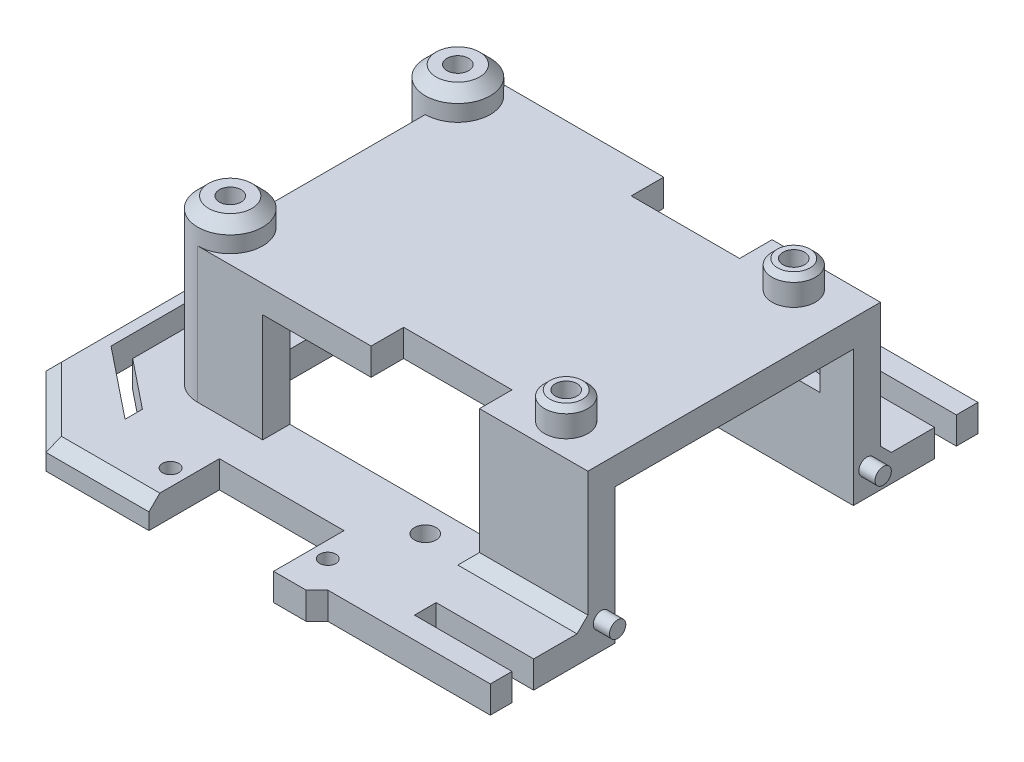
SolidWorks part; units mm, degrees
material "Plain Carbon Steel"
ref_plane "Front Plane" through (0, 0, 0) normal (0, 0, 1) x (1, 0, 0)
ref_plane "Top Plane" through (0, 0, 0) normal (0, 1, 0) x (1, 0, 0)
ref_plane "Right Plane" through (0, 0, 0) normal (1, 0, 0) x (0, 0, -1)
sketch "Sketch1" plane through (0, 0, 0) normal (0, 1, 0) x (1, 0, 0)
  line L0 (0, 0) -> (148.3177, 0) construction
  line L1 (0, 34) -> (0, -34)
  line L2 (0, -34) -> (13, -47)
  line L3 (13, -47) -> (32, -47)
  line L4 (32, -47) -> (32, -34)
  line L5 (32, -34) -> (55, -34)
  line L6 (55, -34) -> (55, -47)
  line L7 (55, -47) -> (61, -47)
  line L8 (61, -47) -> (63, -45)
  line L9 (63, -45) -> (93, -45)
  line L10 (93, -45) -> (93, -41)
  line L11 (93, -41) -> (75, -41)
  line L12 (75, -41) -> (75, -37)
  line L13 (75, -37) -> (93, -37)
  line L14 (93, -37) -> (93, -22)
  line L15 (93, -22) -> (33, -22)
  line L16 (33, -22) -> (21, -10)
  line L17 (21, -10) -> (21, 10)
  line L18 (33, 22) -> (21, 10)
  line L19 (93, 22) -> (33, 22)
  line L20 (93, 37) -> (93, 22)
  line L21 (75, 37) -> (93, 37)
  line L22 (75, 41) -> (75, 37)
  line L23 (93, 41) -> (75, 41)
  line L24 (93, 45) -> (93, 41)
  line L25 (63, 45) -> (93, 45)
  line L26 (61, 47) -> (63, 45)
  line L27 (55, 47) -> (61, 47)
  line L28 (55, 34) -> (55, 47)
  line L29 (32, 34) -> (55, 34)
  line L30 (32, 47) -> (32, 34)
  line L31 (13, 47) -> (32, 47)
  line L32 (0, 34) -> (13, 47)
  circle A0 centre (13, -10) radius 2
  circle A1 centre (29, -40) radius 1.5
  circle A2 centre (58, -40) radius 1.5
  circle A3 centre (63, -27) radius 2
  circle A4 centre (13, 10) radius 2
  circle A5 centre (29, 40) radius 1.5
  circle A6 centre (58, 40) radius 1.5
  circle A7 centre (63, 27) radius 2
  point P22 (21, 0)
  point P44 (0, 0)
  dimension "D17" = 4
  dimension "D18" = 3
  dimension "D19" = 4
  dimension "D20" = 3
  dimension "D1" = 34
  dimension "D2" = 13
  dimension "D3" = 22
  dimension "D4" = 37
  dimension "D5" = 23
  dimension "D6" = 2
  dimension "D7" = 6
  dimension "D8" = 2
  dimension "D9" = 43
  dimension "D10" = 4
  dimension "D11" = 93
  dimension "D12" = 10
  dimension "D13" = 45
  dimension "D14" = 72
  dimension "D15" = 43
  dimension "D16" = 61
  dimension "D21" = 3
  dimension "D22" = 10
  dimension "D23" = 3
  dimension "D24" = 30
  dimension "D25" = 54
  dimension "D26" = 6
  dimension "D27" = 6
  dimension "D28" = 80
extrude "Boss-Extrude1" add sketch "Sketch1" along normal blind 5
sketch "Sketch2" plane through (0, 5, 0) normal (0, 1, 0) x (1, 0, 0)
  line L0 (0, 0) -> (79.458, 0) construction
  line L1 (4, 26) -> (4, 12)
  line L2 (8, -8) -> (4, -8)
  line L3 (8, -8) -> (8, 8)
  line L4 (8, 8) -> (4, 8)
  line L5 (4, -8) -> (4, 8)
  line L6 (8, -8) -> (4, 8) construction
  line L7 (8, 8) -> (4, -8) construction
  line L8 (4, 12) -> (8, 12)
  line L9 (8, 12) -> (8, 26)
  line L10 (8, 26) -> (17, 33.2058)
  line L11 (17, 33.2058) -> (17, 36.4083)
  line L12 (17, 36.4083) -> (4, 26)
  line L14 (32, 34) -> (32, 47) construction
  line L16 (0, 34) -> (0, -34) construction
  line L18 (8, -8) -> (4, 8) construction
  line L19 (8, 8) -> (4, -8) construction
  line L20 (17, -36.4083) -> (4, -26)
  line L21 (4, -12) -> (8, -12)
  line L22 (8, -8) -> (4, -8)
  line L23 (8, 8) -> (4, 8)
  line L24 (8, -26) -> (17, -33.2058)
  line L25 (8, -12) -> (8, -26)
  line L26 (4, -26) -> (4, -12)
  line L27 (17, -33.2058) -> (17, -36.4083)
  circle A0 centre (13, 10) radius 2 construction
  point P3 (6, 0)
  point P16 (0, 0)
  point P19 (0, 0)
  point P20 (17, 41.5111)
  point P21 (0, 0)
  dimension "D1" = 2
  dimension "D2" = 2
  dimension "D3" = 4
  dimension "D4" = 2.5
  dimension "D5" = 15
  dimension "D6" = 26
  dimension "D7" = 4
extrude "Cut-Extrude1" cut sketch "Sketch2" against normal blind 5 contours L11 L12 L1 L8 L9 L10 | L5 L2 L3 L4 | L27 L24 L25 L21 L26 L20 region at (10.6728, 5, -30.9883) region at (6, 5, 0) region at (10.6728, 5, 30.9883)
sketch "Sketch3" plane through (0, 5, 0) normal (0, 1, 0) x (1, 0, 0)
  line L0 (93, -22) -> (33, -22) construction
  line L1 (33, 22) -> (93, 22) construction
  line L2 (93, -22) -> (33, -22)
  line L3 (33, 22) -> (93, 22)
  line L4 (93, -27) -> (21, -27)
  line L5 (21, 27) -> (93, 27)
  line L6 (21, -10) -> (21, 10) construction
  line L7 (21, -27) -> (21, 27)
  line L8 (33, 27) -> (93, 27) construction
  line L9 (93, -27) -> (33, -27) construction
  line L10 (93, -37) -> (93, -22) construction
  line L11 (93, 22) -> (93, 37) construction
  line L12 (33, -22) -> (21, -10) construction
  line L13 (21, 10) -> (33, 22) construction
  line L14 (93, -27) -> (93, -22)
  line L15 (93, 22) -> (93, 27)
  line L16 (33, -22) -> (21, -10)
  line L17 (21, 10) -> (33, 22)
  point P9 (21, -27)
  point P10 (21, 30.082)
  point P12 (21, 27)
  point P14 (21, 27.7828)
  point P16 (21.8468, -27)
  dimension "D1" = 5
extrude "Boss-Extrude3" add sketch "Sketch3" along normal blind 25 from surface contours L7 L17 L3 L15 L5 | L2 L16 L7 L4 L14 region at (51.6667, 5, 23.4167) region at (51.6667, 5, -23.4167) starting at face at (9.6667, 5, -24.269)
sketch "Sketch4" plane through (0, 30, 0) normal (0, 1, 0) x (1, 0, 0)
  line L1 (21, 27) -> (93, 27)
  line L2 (21, 27) -> (21, -27)
  line L3 (21, -27) -> (93, -27)
  line L4 (93, 27) -> (93, -27)
extrude "Boss-Extrude4" add sketch "Sketch4" against normal blind 5
sketch "Sketch5" plane through (0, 0, 27) normal (0, 0, 1) x (1, 0, 0)
  line L0 (63, 5) -> (93, 5) construction
  line L1 (33, 25) -> (73, 25)
  line L2 (33, 25) -> (33, 5)
  line L3 (33, 5) -> (73, 5)
  line L4 (73, 25) -> (73, 5)
  line L7 (32, 5) -> (32, 0) construction
  dimension "D1" = 20
  dimension "D2" = 40
  dimension "D3" = 1
extrude "Cut-Extrude2" cut sketch "Sketch5" against normal through all
sketch "Sketch6" plane through (0, 30, 0) normal (0, 1, 0) x (1, 0, 0)
  line L0 (93, 27) -> (21, 27) construction
  line L1 (73, 27) -> (53, 27)
  line L2 (73, 27) -> (73, 21)
  line L3 (73, 21) -> (53, 21)
  line L4 (53, 27) -> (53, 21)
  line L5 (73, 27) -> (73, 22) construction
  line L6 (21, 0) -> (93, 0)
  line L7 (21, 27) -> (21, -27) construction
  line L8 (93, 27) -> (93, -27) construction
  line L9 (53, -27) -> (53, -21)
  line L10 (73, -21) -> (53, -21)
  line L11 (73, -27) -> (73, -21)
  line L12 (73, -27) -> (53, -27)
  line M5 (21, -27) -> (93, -27)
  line M7 (93, 27) -> (21, 27)
  dimension "D1" = 20
  dimension "D2" = 6
extrude "Cut-Extrude4" cut sketch "Sketch6" against normal blind 10 contours L4 L3 L2 M7 | L11 L10 L9 M5 region at (63, 30, -24) region at (63, 30, 24)
sketch "Sketch7" plane through (0, 25, 0) normal (0, -1, 0) x (1, 0, 0)
  line L1 (93, 22) -> (93, -22) construction
  line L2 (21, 0) -> (93, 0) construction
  line L3 (21, 10) -> (21, -10) construction
  circle A0 centre (83, 21) radius 4
  circle A1 centre (83, -21) radius 4
  dimension "D1" = 8
  dimension "D2" = 10
  dimension "D3" = 21
extrude "Boss-Extrude5" add sketch "Sketch7" against normal blind 5 from surface starting at face at (61, 30, 0)
sketch "Sketch8" plane through (0, 35, 0) normal (0, 1, 0) x (1, 0, 0)
  circle A0 centre (83, 21) radius 2
  dimension "D1" = 4
extrude "Cut-Extrude5" cut sketch "Sketch8" against normal up to surface (10 mm away) contours A0 region at (83, 35, -21) up to face at (54, 25, 0)
sketch "Sketch9" plane through (0, 25, 0) normal (0, -1, 0) x (1, 0, 0)
  circle A0 centre (83, -21) radius 4
  point P3 (83, -21)
  dimension "D1" = 8
extrude "Cut-Extrude6" cut sketch "Sketch9" along normal blind 10
sketch "Sketch10" plane through (0, 30, 0) normal (0, 1, 0) x (1, 0, 0)
  line L1 (53, 27) -> (21, 27) construction
  line L2 (21, 27) -> (21, -27) construction
  circle A0 centre (21, 21) radius 6
  point P2 (21, 21)
  dimension "D1" = 12
extrude "Boss-Extrude6" add sketch "Sketch10" against normal blind 30 from offset 5
sketch "Sketch11" plane through (0, 35, 0) normal (0, 1, 0) x (1, 0, 0)
  circle A0 centre (21, 21) radius 2
  dimension "D1" = 4
extrude "Cut-Extrude7" cut sketch "Sketch11" against normal blind 10 contours A0 region at (21, 35, -21)
sketch "Sketch12" plane through (0, 5, 0) normal (0, 1, 0) x (1, 0, 0)
  circle A0 centre (21, 21) radius 4.5
  dimension "D1" = 9
extrude "Cut-Extrude8" cut sketch "Sketch12" against normal through all from surface starting at face at (21, 25, -19)
sketch "Sketch13" plane through (93, 0, 0) normal (1, 0, 0) x (0, 0, -1)
  line L0 (22, 5) -> (22, 0) construction
  line L1 (27, 5) -> (37, 5) construction
  circle A0 centre (24.5, 5) radius 1.5
  point P3 (0, 0)
  dimension "D2" = 3
  dimension "D1" = 2.5
mirror "Mirror11" about plane through (0, 0, 0) normal (0, 0, 1) of "Cut-Extrude5", "Cut-Extrude6"
mirror "Mirror12" about plane through (0, 0, 0) normal (0, 0, 1) of "Boss-Extrude6"
mirror "Mirror16" about plane through (0, 0, 0) normal (0, 0, 1) of "Cut-Extrude7"
sketch "Sketch14" plane through (0, 25, 0) normal (0, 1, 0) x (1, 0, 0)
  circle A0 centre (21, -21) radius 4.5
  dimension "D1" = 9
extrude "Cut-Extrude11" cut sketch "Sketch14" along direction (0, 1, 0) on the side against the normal through all
extrude "Boss-Extrude8" add sketch "Sketch13" along normal blind 3 contours A0
mirror "Mirror19" about plane through (0, 0, 0) normal (0, 0, 1) of "Boss-Extrude8"
chamfer "Chamfer2" distance 1 angle 45 2 edges at (83, 35, -25) (83, 35, 17)
chamfer "Chamfer3" distance 2 angle 45 7 edges at (22.5, 5, -47) (6.5, 5, -40.5) (0, 5, 0) (6.5, 5, 40.5) (22.5, 5, 47) (21, 35, -15) (21, 35, 15)
chamfer "Chamfer4" distance 2 angle 45 4 edges at (73, 5, -24.5) (83, 5, -27) (73, 5, 24.5) (83, 5, 27)
chamfer "Chamfer5" distance 2 angle 45 2 edges at (83, 25, -19) (83, 25, 23)
